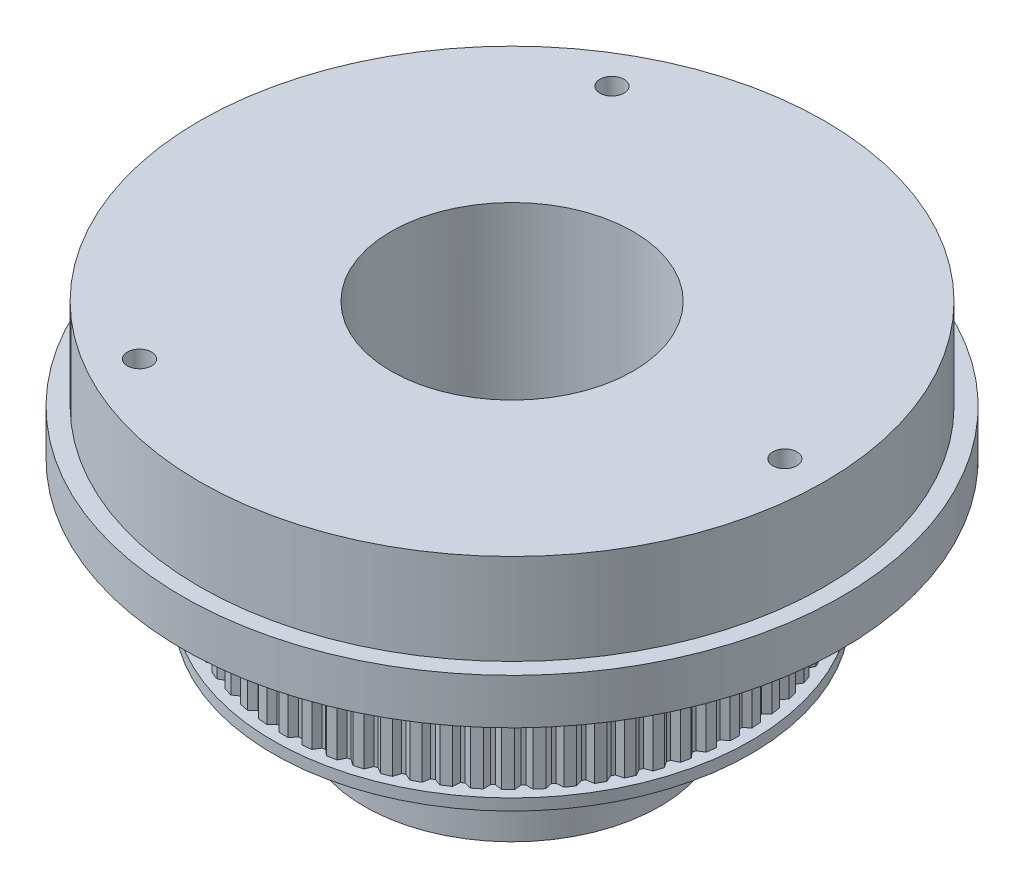
SolidWorks part; units mm, degrees
ref_plane "Front Plane" through (0, 0, 0) normal (0, 0, 1) x (1, 0, 0)
ref_plane "Top Plane" through (0, 0, 0) normal (0, 1, 0) x (1, 0, 0)
ref_plane "Right Plane" through (0, 0, 0) normal (1, 0, 0) x (0, 0, -1)
sketch "Sketch1" plane through (0, 0, 0) normal (0, 1, 0) x (1, 0, 0)
  line L0 (-82.0157, 0) -> (82.2392, 0) construction
  line L1 (0, -19.2539) -> (0, 22.604) construction
  circle A0 centre (0, 0) radius 13.5255
  circle A1 centre (0, 0) radius 24.892
  point P22 (0, 0)
  dimension "D1" = 27.051
  dimension "D2" = 49.784
extrude "Boss-Extrude1" add sketch "Sketch1" along normal blind 19.05
sketch "Sketch2" plane through (0, 0, 0) normal (0, -1, 0) x (1, 0, 0)
  circle A0 centre (0, 0) radius 26.67
  dimension "D1" = 53.34
extrude "Boss-Extrude2" add sketch "Sketch2" along normal blind 1.27
sketch "Sketch3" plane through (0, 0, 0) normal (0, 1, 0) x (1, 0, 0)
  circle A0 centre (0, 0) radius 13.5255
  circle A1 centre (0, 0) radius 26.67 construction
  dimension "D1" = 27.051
  dimension "D2" = 0
extrude "Cut-Extrude1" cut sketch "Sketch3" against normal up to next
sketch "Sketch14" plane through (0, 19.05, 0) normal (0, 1, 0) x (1, 0, 0)
  line L0 (0, 0) -> (0, -25.527) construction
  line L1 (0.508, -25.5219) -> (1.016, -24.8713)
  line L2 (-0.508, -25.5219) -> (-1.016, -24.8713)
  line L3 (-1.9576, -25.4518) -> (-1.3892, -24.8532)
  line L4 (-4.4049, -25.1441) -> (-3.7814, -24.6031)
  line L5 (-6.8111, -24.6016) -> (-6.1383, -24.1233)
  line L6 (-9.1537, -23.8293) -> (-8.4378, -23.4183)
  line L7 (-11.4108, -22.8346) -> (-10.6586, -22.4946)
  line L8 (-13.5614, -21.6267) -> (-12.7799, -21.3608)
  line L9 (-15.5854, -20.2169) -> (-14.7819, -20.0277)
  line L10 (-17.4638, -18.6183) -> (-16.6458, -18.5075)
  line L11 (-19.1792, -16.8459) -> (-18.3543, -16.8146)
  line L12 (-20.7156, -14.9162) -> (-19.8915, -14.9646)
  line L13 (-22.0585, -12.8472) -> (-21.2429, -12.975)
  line L14 (-23.1954, -10.6583) -> (-22.396, -10.8642)
  line L15 (-24.1158, -8.3699) -> (-23.34, -8.6519)
  line L16 (-24.8111, -6.0033) -> (-24.0661, -6.3589)
  line L17 (-25.2746, -3.5806) -> (-24.5675, -4.0065)
  line L18 (-25.5022, -1.1246) -> (-24.8394, -1.6167)
  line L19 (-25.4917, 1.342) -> (-24.8795, 0.7882)
  line L20 (-25.2432, 3.7961) -> (-24.6873, 3.1858)
  line L21 (-24.759, 6.2146) -> (-24.2646, 5.5535)
  line L22 (-24.0436, 8.5752) -> (-23.6153, 7.8695)
  line L23 (-23.1037, 10.8557) -> (-22.7455, 10.112)
  line L24 (-21.9481, 13.0349) -> (-21.6634, 12.26)
  line L25 (-20.5876, 15.0923) -> (-20.379, 14.2936)
  line L26 (-19.0349, 17.0089) -> (-18.9044, 16.1937)
  line L27 (-17.3044, 18.7666) -> (-17.2532, 17.9427)
  line L28 (-15.4124, 20.3491) -> (-15.4409, 19.5241)
  line L29 (-13.3765, 21.7416) -> (-13.4845, 20.9232)
  line L30 (-11.2157, 22.9311) -> (-11.4022, 22.127)
  line L31 (-8.9501, 23.9065) -> (-9.2134, 23.1241)
  line L32 (-6.601, 24.6588) -> (-6.9386, 23.9054)
  line L33 (-4.1903, 25.1807) -> (-4.599, 24.4635)
  line L34 (-1.7405, 25.4676) -> (-2.2164, 24.7931)
  line L35 (0.7256, 25.5167) -> (0.1868, 24.8913)
  line L36 (3.185, 25.3275) -> (2.5883, 24.7571)
  line L37 (5.6146, 24.9019) -> (4.9656, 24.3917)
  line L38 (7.9917, 24.2438) -> (7.2966, 23.7986)
  line L39 (10.2943, 23.3593) -> (9.5594, 22.9832)
  line L40 (12.5007, 22.2567) -> (11.733, 21.9533)
  line L41 (14.5904, 20.9463) -> (13.797, 20.7185)
  line L42 (16.5439, 19.4403) -> (15.7322, 19.2901)
  line L43 (18.343, 17.7528) -> (17.5205, 17.6817)
  line L44 (19.9707, 15.8996) -> (19.1453, 15.9082)
  line L45 (21.412, 13.8979) -> (20.5913, 13.9861)
  line L46 (22.6534, 11.7665) -> (21.845, 11.9335)
  line L47 (23.6833, 9.5252) -> (22.8948, 9.7694)
  line L48 (24.492, 7.195) -> (23.7308, 7.5142)
  line L49 (25.0721, 4.7975) -> (24.3452, 5.1887)
  line L50 (25.4181, 2.3553) -> (24.7323, 2.8149)
  line L51 (25.5268, -0.1089) -> (24.8885, 0.4147)
  line L52 (25.3971, -2.572) -> (24.8124, -1.9893)
  line L53 (25.0303, -5.0112) -> (24.5046, -4.3748)
  line L54 (24.4298, -7.4036) -> (23.9679, -6.7194)
  line L55 (23.6012, -9.7268) -> (23.2075, -9.0012)
  line L56 (22.5522, -11.9593) -> (22.2304, -11.1991)
  line L57 (21.2927, -14.08) -> (21.0458, -13.2923)
  line L58 (19.8344, -16.0694) -> (19.6647, -15.2615)
  line L59 (18.1909, -17.9086) -> (18.0999, -17.0882)
  line L60 (16.3775, -19.5807) -> (16.3662, -18.7553)
  line L61 (14.4113, -21.07) -> (14.4796, -20.2473)
  line L62 (12.3105, -22.3625) -> (12.4579, -21.5502)
  line L63 (10.0947, -23.4462) -> (10.3198, -22.652)
  line L64 (7.7847, -24.311) -> (8.0854, -23.5423)
  line L65 (5.402, -24.9489) -> (5.7755, -24.2127)
  line L66 (2.9689, -25.3538) -> (3.4117, -24.6571)
  line L67 (-2.9689, -25.3538) -> (-3.4117, -24.6571)
  line L68 (-5.402, -24.9489) -> (-5.7755, -24.2127)
  line L69 (-7.7847, -24.311) -> (-8.0854, -23.5423)
  line L70 (-10.0947, -23.4462) -> (-10.3198, -22.652)
  line L71 (-12.3105, -22.3625) -> (-12.4579, -21.5502)
  line L72 (-14.4113, -21.07) -> (-14.4796, -20.2473)
  line L73 (-16.3775, -19.5807) -> (-16.3662, -18.7553)
  line L74 (-18.1909, -17.9086) -> (-18.0999, -17.0882)
  line L75 (-19.8344, -16.0694) -> (-19.6647, -15.2615)
  line L76 (-21.2927, -14.08) -> (-21.0458, -13.2923)
  line L77 (-22.5522, -11.9593) -> (-22.2304, -11.1991)
  line L78 (-23.6012, -9.7268) -> (-23.2075, -9.0012)
  line L79 (-24.4298, -7.4036) -> (-23.9679, -6.7194)
  line L80 (-25.0303, -5.0112) -> (-24.5046, -4.3748)
  line L81 (-25.3971, -2.572) -> (-24.8124, -1.9893)
  line L82 (-25.5268, -0.1089) -> (-24.8885, 0.4147)
  line L83 (-25.4181, 2.3553) -> (-24.7323, 2.8149)
  line L84 (-25.0721, 4.7975) -> (-24.3452, 5.1887)
  line L85 (-24.492, 7.195) -> (-23.7308, 7.5142)
  line L86 (-23.6833, 9.5252) -> (-22.8948, 9.7694)
  line L87 (-22.6534, 11.7665) -> (-21.845, 11.9335)
  line L88 (-21.412, 13.8979) -> (-20.5913, 13.9861)
  line L89 (-19.9707, 15.8996) -> (-19.1453, 15.9082)
  line L90 (-18.343, 17.7528) -> (-17.5205, 17.6817)
  line L91 (-16.5439, 19.4403) -> (-15.7322, 19.2901)
  line L92 (-14.5904, 20.9463) -> (-13.797, 20.7185)
  line L93 (-12.5007, 22.2567) -> (-11.733, 21.9533)
  line L94 (-10.2943, 23.3593) -> (-9.5594, 22.9832)
  line L95 (-7.9917, 24.2438) -> (-7.2966, 23.7986)
  line L96 (-5.6146, 24.9019) -> (-4.9656, 24.3917)
  line L97 (-3.185, 25.3275) -> (-2.5883, 24.7571)
  line L98 (-0.7256, 25.5167) -> (-0.1868, 24.8913)
  line L99 (1.7405, 25.4676) -> (2.2164, 24.7931)
  line L100 (4.1903, 25.1807) -> (4.599, 24.4635)
  line L101 (6.601, 24.6588) -> (6.9386, 23.9054)
  line L102 (8.9501, 23.9065) -> (9.2134, 23.1241)
  line L103 (11.2157, 22.9311) -> (11.4022, 22.127)
  line L104 (13.3765, 21.7416) -> (13.4845, 20.9232)
  line L105 (15.4124, 20.3491) -> (15.4409, 19.5241)
  line L106 (17.3044, 18.7666) -> (17.2532, 17.9427)
  line L107 (19.0349, 17.0089) -> (18.9044, 16.1937)
  line L108 (20.5876, 15.0923) -> (20.379, 14.2936)
  line L109 (21.9481, 13.0349) -> (21.6634, 12.26)
  line L110 (23.1037, 10.8557) -> (22.7455, 10.112)
  line L111 (24.0436, 8.5752) -> (23.6153, 7.8695)
  line L112 (24.759, 6.2146) -> (24.2646, 5.5535)
  line L113 (25.2432, 3.7961) -> (24.6873, 3.1858)
  line L114 (25.4917, 1.342) -> (24.8795, 0.7882)
  line L115 (25.5022, -1.1246) -> (24.8394, -1.6167)
  line L116 (25.2746, -3.5806) -> (24.5675, -4.0065)
  line L117 (24.8111, -6.0033) -> (24.0661, -6.3589)
  line L118 (24.1158, -8.3699) -> (23.34, -8.6519)
  line L119 (23.1954, -10.6583) -> (22.396, -10.8642)
  line L120 (22.0585, -12.8472) -> (21.2429, -12.975)
  line L121 (20.7156, -14.9162) -> (19.8915, -14.9646)
  line L122 (19.1792, -16.8459) -> (18.3543, -16.8146)
  line L123 (17.4638, -18.6183) -> (16.6458, -18.5075)
  line L124 (15.5854, -20.2169) -> (14.7819, -20.0277)
  line L125 (13.5614, -21.6267) -> (12.7799, -21.3608)
  line L126 (11.4108, -22.8346) -> (10.6586, -22.4946)
  line L127 (9.1537, -23.8293) -> (8.4378, -23.4183)
  line L128 (6.8111, -24.6016) -> (6.1383, -24.1233)
  line L129 (4.4049, -25.1441) -> (3.7814, -24.6031)
  line L130 (1.9576, -25.4518) -> (1.3892, -24.8532)
  circle A0 centre (0, 0) radius 25.527
  circle A1 centre (0, 0) radius 24.892
  point P140 (0, 0)
  point P268 (0, 0)
  circle M3 centre (0, 0) radius 24.892
  dimension "D1" = 49.784
  dimension "D2" = 51.054
  dimension "D3" = 0.508
  dimension "D4" = 1.016
  dimension "D5" = 65
extrude "Boss-Extrude6" add sketch "Sketch14" against normal up to surface (19.05 mm away) contours L109 A0 L45 M3 | L110 A0 L46 M3 | L111 A0 L47 M3 | L112 A0 L48 M3 | L113 A0 L49 M3 | L114 A0 L50 M3 | L115 A0 L51 M3 | L116 A0 L52 M3 | L117 A0 L53 M3 | L118 A0 L54 M3 | L119 A0 L55 M3 | L120 A0 L56 M3 | L121 A0 L57 M3 | L122 A0 L58 M3 | L123 A0 L59 M3 | L124 A0 L60 M3 | L125 A0 L61 M3 | L126 A0 L62 M3 | L127 A0 L63 M3 | L128 A0 L64 M3 | L129 A0 L65 M3 | L130 A0 L66 M3 | A1 L0 A0 L1 | L67 A0 L3 M3 | L0 L2 A0 M3 | L68 A0 L4 M3 | L69 A0 L5 M3 | L70 A0 L6 M3 | L71 A0 L7 M3 | L72 A0 L8 M3 | L73 A0 L9 M3 | L74 A0 L10 M3 | L75 A0 L11 M3 | L76 A0 L12 M3 | L77 A0 L13 M3 | L78 A0 L14 M3 | L79 A0 L15 M3 | L80 A0 L16 M3 | L81 A0 L17 M3 | L82 A0 L18 M3 | L83 A0 L19 M3 | L84 A0 L20 M3 | L85 A0 L21 M3 | L86 A0 L22 M3 | L87 A0 L23 M3 | L88 A0 L24 M3 | L89 A0 L25 M3 | L90 A0 L26 M3 | L91 A0 L27 M3 | L92 A0 L28 M3 | L93 A0 L29 M3 | L94 A0 L30 M3 | L95 A0 L31 M3 | L96 A0 L32 M3 | L97 A0 L33 M3 | L98 A0 L34 M3 | L99 A0 L35 M3 | L100 A0 L36 M3 | L101 A0 L37 M3 | L102 A0 L38 M3 | L103 A0 L39 M3 | L104 A0 L40 M3 | L108 A0 L44 M3 | L107 A0 L43 M3 | L106 A0 L42 M3 | L105 A0 L41 M3 up to face at (0, 0, -26.67)
sketch "Sketch4" plane through (0, -1.27, 0) normal (0, -1, 0) x (1, 0, 0)
  line L0 (-8.777, -13.9837) -> (-8.777, -21.7693)
  line L1 (8.4428, 14.188) -> (-8.777, 14.188)
  line L2 (8.4428, 14.188) -> (8.4428, -13.9837)
  line L3 (8.4428, -13.9837) -> (-8.777, -13.9837)
  line L4 (-8.777, 14.188) -> (-8.777, -13.9837)
  line L5 (-8.777, -21.7693) -> (-6.237, -21.7693)
  line L6 (-6.237, -21.7693) -> (-6.237, -13.9837)
  line L7 (8.4428, -13.9837) -> (8.4428, -21.7693)
  line L8 (8.4428, -21.7693) -> (5.9028, -21.7693)
  line L9 (5.9028, -21.7693) -> (5.9028, -13.9837)
  circle A0 centre (0, 0) radius 13.462
  circle A1 centre (0, 0) radius 16.51
  circle M1 centre (0, 0) radius 13.5255
  dimension "D1" = 26.924
  dimension "D2" = 33.02
  dimension "D3" = 2.54
  dimension "D4" = 2.54
extrude "Boss-Extrude3" add sketch "Sketch4" along normal blind 10.16 contours L4 A1 M1 | L1 A1 | L1 A1 L4 L2 M1 | L9 A1 L7 L3 | L4 L3 L2 M1 | L3 A1 L6 | L7 A1 L2 M1 | L6 A1 L9 L3
sketch "Sketch8" plane through (0, 19.05, 0) normal (0, 1, 0) x (1, 0, 0)
  circle A0 centre (0, 21.59) radius 2.54
  circle A1 centre (15.2664, 15.2664) radius 2.54
  circle A2 centre (21.59, 0) radius 2.54
  circle A3 centre (15.2664, -15.2664) radius 2.54
  circle A4 centre (0, -21.59) radius 2.54
  circle A5 centre (-15.2664, -15.2664) radius 2.54
  circle A6 centre (-21.59, 0) radius 2.54
  circle A7 centre (-15.2664, 15.2664) radius 2.54
  point P19 (0, 0)
  dimension "D1" = 21.59
  dimension "D2" = 5.08
  dimension "D3" = 8
hole_wizard "Tap Drill for M3x0.5 Tap2" [suppressed] positions "Sketch9" profile "Sketch10" hole size "M3x0.5" standard "ANSI Metric"
sketch "Sketch9" plane through (0, 19.05, 0) normal (0, 1, 0) x (1, 0, 0)
  point P0 (0, -21.59)
  point P3 (-15.2664, -15.2664)
  point P6 (-21.59, 0)
  point P9 (-15.2664, 15.2664)
  point P12 (0, 21.59)
  point P15 (15.2664, 15.2664)
  point P18 (21.59, 0)
  point P21 (15.2664, -15.2664)
sketch "Sketch10" plane through (0, 19.05, 21.59) normal (1, 0, 0) x (0, 0, 1)
  line L0 (0, 0) -> (0, 25.4)
  line L1 (0, 25.4) -> (1.25, 25.4)
  line L2 (1.25, 25.4) -> (1.25, 0)
  line L5 (1.25, 0) -> (0, 0)
  line L11 (0, -6.35) -> (0, 107.95) construction
  dimension "Thru Hole Dia." = 2.5
  dimension "Thru Hole Depth" = 25.4
hole_wizard "M3x0.5 Tapped Hole2" positions "3DSketch1" profile "Sketch11" tap size "M3x0.5" standard "ANSI Metric" end condition through all
sketch3d "3DSketch1"
  point P0 (15.5083, -6.0745, -5.6632)
sketch "Sketch11" plane through (15.5083, -6.0745, -5.6632) normal (0, 1, 0) x (-0.343, 0, -0.9393)
  line L0 (0, 0) -> (0, 50.7101)
  line L1 (0, 50.7101) -> (1.3, 50.7101)
  line L2 (1.3, 50.7101) -> (1.3, 0)
  line L5 (1.3, 0) -> (0, 0)
  line L11 (0, -6.35) -> (0, 107.95) construction
  dimension "Thread Major Dia." = 2.6
  dimension "Thru Tap Drill Depth" = 50.7101
sketch "Sketch12" plane through (0, 19.05, 0) normal (0, 1, 0) x (1, 0, 0)
  circle A0 centre (0, 0) radius 34.925
  circle A1 centre (0, 0) radius 13.5255
  dimension "D1" = 69.85
  dimension "D2" = 27.051
extrude "Boss-Extrude4" add sketch "Sketch12" along normal blind 10.16
sketch "Sketch15" plane through (0, 19.05, 0) normal (0, -1, 0) x (1, 0, 0)
  circle A0 centre (0, 0) radius 36.83
  circle A1 centre (0, 0) radius 24.892
  dimension "D1" = 73.66
  dimension "D2" = 49.784
extrude "Boss-Extrude7" add sketch "Sketch15" along normal blind 5.08
sketch "Sketch16" plane through (0, 29.21, 0) normal (0, 1, 0) x (1, 0, 0)
  circle A0 centre (30.48, 0) radius 2.9786
  circle A1 centre (-15.24, -26.3965) radius 2.9786
  circle A2 centre (-15.24, 26.3965) radius 2.9786
  point P9 (0, 0)
  dimension "D1" = 30.48
  dimension "D3" = 5.9573
  dimension "D2" = 3
hole_wizard "M3x0.5 Tapped Hole1" positions "Sketch19" profile "Sketch20" tap size "M3x0.5" standard "ANSI Metric" end condition through all
sketch "Sketch19" plane through (0, 29.21, 0) normal (0, 1, 0) x (1, 0, 0)
  point P0 (30.48, 0)
  point P3 (-15.24, -26.3965)
  point P6 (-15.24, 26.3965)
sketch "Sketch20" plane through (30.48, 29.21, 0) normal (1, 0, 0) x (0, 0, 1)
  line L0 (0, 0) -> (0, 40.64)
  line L1 (0, 40.64) -> (1.35, 40.64)
  line L2 (1.35, 40.64) -> (1.35, 0)
  line L5 (1.35, 0) -> (0, 0)
  line L11 (0, -6.35) -> (0, 107.95) construction
  dimension "Thread Major Dia." = 2.7
  dimension "Thru Tap Drill Depth" = 40.64
